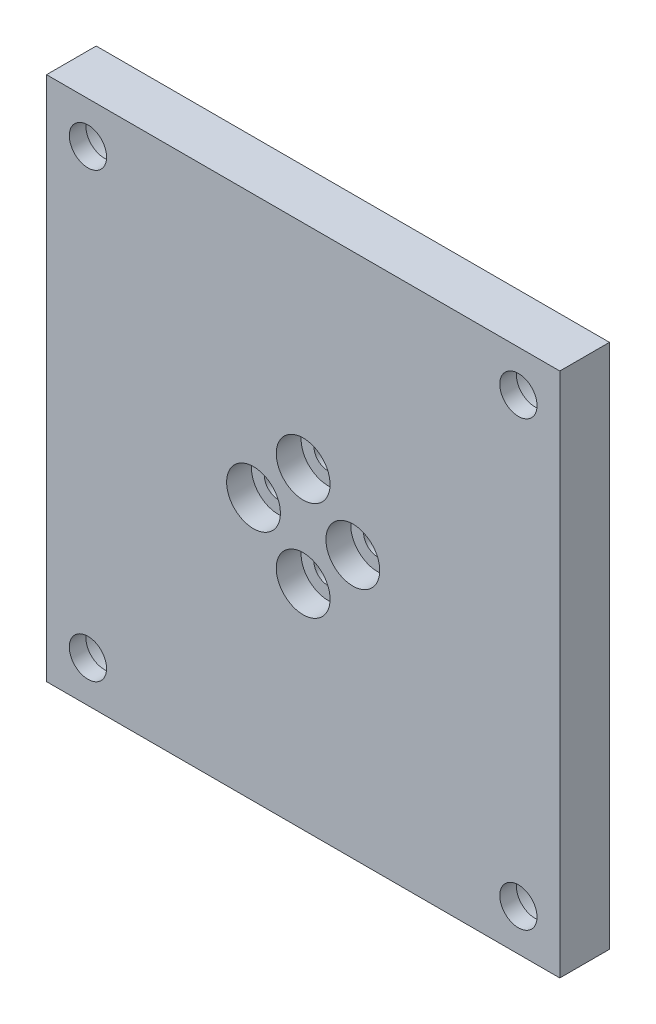
SolidWorks part; units mm, degrees
material "Сплав 2024"
ref_plane "Спереди" through (0, 0, 0) normal (0, 0, 1) x (1, 0, 0)
ref_plane "Сверху" through (0, 0, 0) normal (0, 1, 0) x (1, 0, 0)
ref_plane "Справа" through (0, 0, 0) normal (1, 0, 0) x (0, 0, -1)
sketch "Эскиз1" plane through (0, 0, 0) normal (0, 0, 1) x (1, 0, 0)
  line L1 (-31, 31.75) -> (31, 31.75)
  line L2 (-31, 31.75) -> (-31, -31.75)
  line L3 (-31, -31.75) -> (31, -31.75)
  line L4 (31, 31.75) -> (31, -31.75)
  line L5 (-31, 31.75) -> (31, -31.75) construction
  line L6 (-31, -31.75) -> (31, 31.75) construction
  point P0 (0, 0)
  dimension "D1" = 62
  dimension "D2" = 63.5
extrude "Бобышка-Вытянуть1" add sketch "Эскиз1" along normal blind 6
sketch "Эскиз2" plane through (0, 0, 6) normal (0, 0, 1) x (1, 0, 0)
  line L0 (-26, 31.75) -> (-26, -31.75) construction
  line L1 (31, 31.75) -> (-31, 31.75) construction
  line L2 (-31, -31.75) -> (31, -31.75) construction
  line L3 (26, 31.75) -> (26, -31.75) construction
  line L4 (-31, 26.75) -> (31, 26.75) construction
  line L5 (-31, 31.75) -> (-31, -31.75) construction
  line L6 (31, -31.75) -> (31, 31.75) construction
  line L7 (31, -26.75) -> (-31, -26.75) construction
  line L8 (0, 31.75) -> (0, -31.75) construction
  line L9 (-31, 0) -> (31, 0) construction
  circle A0 centre (0, 0) radius 6 construction
  dimension "D5" = 12
  dimension "D1" = 5
  dimension "D2" = 5
  dimension "D3" = 5
  dimension "D4" = 5
hole_wizard "Цековка для винта с внутренним шестигранником M31" positions "Эскиз4" profile "Эскиз3" counterbore size "M3" standard "Ansi Metric" end condition through all
sketch "Эскиз4" plane through (0, 0, 6) normal (0, 0, 1) x (1, 0, 0)
  line L0 (0, 31.75) -> (0, -31.75) construction
  line L1 (-31, 0) -> (31, 0) construction
  circle A0 centre (0, 0) radius 6 construction
  point P0 (0, 6)
  point P6 (-6, 0)
  point P10 (0, -6)
  point P12 (6, 0)
sketch "Эскиз3" plane through (0, 6, 6) normal (1, 0, 0) x (0, -1, 0)
  line L0 (0, 0) -> (0, 6)
  line L1 (0, 6) -> (1.7, 6)
  line L3 (1.7, 6) -> (1.7, 3)
  line L4 (1.7, 3) -> (3.25, 3)
  line L5 (3.25, 3) -> (3.25, 0)
  line L7 (3.25, 0) -> (0, 0)
  line L11 (0, -6.35) -> (0, 107.95) construction
  dimension "Диаметр сквозного отверстия" = 3.4
  dimension "Глубина сквозного отверстия" = 6
  dimension "Диаметр цековки" = 6.5
  dimension "Глубина цековки" = 3
hole_wizard "Цековка для винта с внутренним шестигранником M41" positions "Эскиз6" profile "Эскиз5" counterbore size "M4" standard "Ansi Metric" end condition through all
sketch "Эскиз6" plane through (0, 0, 0) normal (0, 0, -1) x (-1, 0, 0)
  line L0 (-26, 31.75) -> (-26, -31.75) construction
  line L1 (31, 26.75) -> (-31, 26.75) construction
  line L2 (-31, -26.75) -> (31, -26.75) construction
  line L3 (26, 31.75) -> (26, -31.75) construction
  point P0 (-26, 26.75)
  point P6 (-26, -26.75)
  point P10 (26, -26.75)
  point P14 (26, 26.75)
sketch "Эскиз5" plane through (26, 26.75, 0) normal (1, 0, 0) x (0, 1, 0)
  line L0 (0, 0) -> (0, 6)
  line L1 (0, 6) -> (2.25, 6)
  line L3 (2.25, 6) -> (2.25, 4)
  line L4 (2.25, 4) -> (4, 4)
  line L5 (4, 4) -> (4, 0)
  line L7 (4, 0) -> (0, 0)
  line L11 (0, -6.35) -> (0, 107.95) construction
  dimension "Диаметр сквозного отверстия" = 4.5
  dimension "Глубина сквозного отверстия" = 6
  dimension "Диаметр цековки" = 8
  dimension "Глубина цековки" = 4
